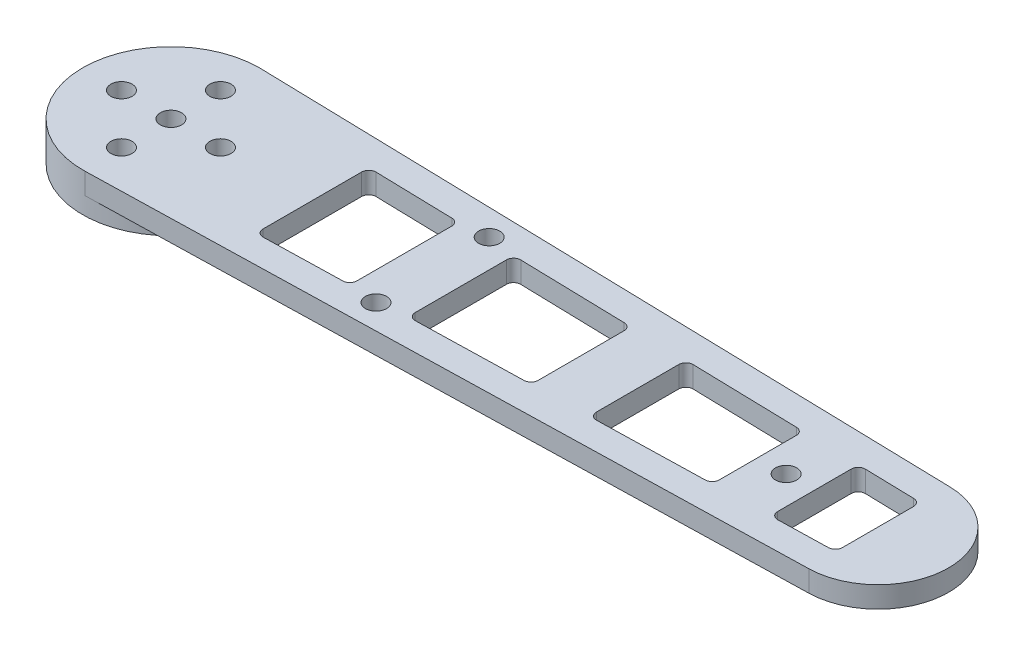
SolidWorks part; units mm, degrees
material "ABS"
ref_plane "前视基准面" through (0, 0, 0) normal (0, 0, 1) x (1, 0, 0)
ref_plane "上视基准面" through (0, 0, 0) normal (0, 1, 0) x (1, 0, 0)
ref_plane "右视基准面" through (0, 0, 0) normal (1, 0, 0) x (0, 0, -1)
sketch "草图1" plane through (0, 0, 0) normal (0, 1, 0) x (1, 0, 0)
  line L0 (-16.855, 0) -> (100, 0) construction
  line L1 (0.3125, 12.4961) -> (100.25, 9.9969)
  line L2 (0.3125, -12.4961) -> (100.25, -9.9969)
  circle A0 centre (0, 0) radius 12.5
  circle A1 centre (100, 0) radius 10
  circle A2 centre (-7, 0) radius 1.5
  circle A3 centre (0, 7) radius 1.5
  circle A4 centre (7, 0) radius 1.5
  circle A5 centre (0, -7) radius 1.5
  circle A6 centre (0, 0) radius 1.5
  dimension "D1" = 25
  dimension "D2" = 100
  dimension "D3" = 20
  dimension "D4" = 7
  dimension "D5" = 3
  dimension "D7" = 3
  dimension "D6" = 4
extrude "凸台-拉伸1" add sketch "草图1" along normal blind 3 contours A0 L0 A1 L1 | L0 A0 L2 A1 | A1 | A0 L0 A2 A4 A3 | L0 A0 A4 A2 A5 region at (0, 0, -5.4699) region at (0, 0, 5.4699) region at (49.7914, 0, -5.8152) region at (49.7914, 0, 5.8152) region at (93.2154, 0, -6.9564)
sketch "草图2" plane through (0, 0, 0) normal (0, -1, 0) x (1, 0, 0)
  circle A0 centre (0, 0) radius 12.5
  circle A1 centre (0, 0) radius 10
  dimension "D1" = 25
  dimension "D2" = 20
extrude "凸台-拉伸2" add sketch "草图2" along normal blind 2.5 contours A0 | A1
sketch "草图3" plane through (0, 3, 0) normal (0, 1, 0) x (1, 0, 0)
  line L0 (-21.5992, 0) -> (131.7448, 0) construction
  line L1 (20, 8.0025) -> (20, -8.0025)
  line L2 (20, 8.0025) -> (95.3937, 6.1171)
  line L3 (20, -8.0025) -> (100, -6.0019)
  line L4 (0.3125, 12.4961) -> (100.25, 9.9969) construction
  line L5 (0.3125, -12.4961) -> (100.25, -9.9969) construction
  line L6 (33, 7.6774) -> (33, -7.6774)
  line L7 (41, 7.4773) -> (41, -7.4773)
  line L8 (58, 7.0522) -> (58, -7.0522)
  line L9 (66, 6.8521) -> (66, -6.8521)
  line L10 (83, 6.427) -> (83, -6.427)
  line L11 (91, 6.2269) -> (91, -6.2269)
  line L12 (100, -6.0019) -> (100, 6.0019)
  line L13 (95.3937, 6.1171) -> (100, 6.0019)
  circle A1 centre (87, 0) radius 1.5
  circle A2 centre (37, 8) radius 1.5
  circle A3 centre (37, -8) radius 1.5
  point P5 (20, 0)
  dimension "D1" = 20
  dimension "D5" = 8
  dimension "D11" = 100
  dimension "D12" = 3
  dimension "D14" = 3
  dimension "D2" = 4
  dimension "D3" = 33
  dimension "D4" = 8
  dimension "D6" = 37
  dimension "D7" = 58
  dimension "D8" = 8
  dimension "83" = 83
  dimension "D10" = 8
  dimension "D13" = 4
extrude "切除-拉伸1" cut sketch "草图3" against normal blind 10 contours L1 L0 L6 L2 | L0 L1 L3 L6 | L2 A2 | L2 A2 | A3 L3 | A3 L3 | L7 L0 L8 L2 | L0 L7 L3 L8 | L9 L0 L10 L2 | L0 L9 L3 L10 | A1 L0 | L0 A1 | L11 L0 L12 L13 L2 | L0 L11 L3 L12 region at (26.4551, 3, -3.9205) region at (26.4551, 3, 3.9205) region at (49.4171, 3, -3.6334) region at (49.4171, 3, 3.6334) region at (37.0104, 3, -8.4153) region at (36.9782, 3, -7.1299) region at (36.9782, 3, 7.1299) region at (37.0104, 3, 8.4153) region at (74.4093, 3, -3.3209) region at (74.4093, 3, 3.3209) region at (87, 3, -0.6366) region at (87, 3, 0.6366) region at (95.4724, 3, -3.0576) region at (95.4724, 3, 3.0576)
fillet "圆角1" radius 1 16 edges at (100, 1.5, 6.0019) (91, 1.5, -6.2269) (100, 1.5, -6.0019) (91, 1.5, 6.2269) (66, 1.5, 6.8521) (83, 1.5, 6.427) (83, 1.5, -6.427) (66, 1.5, -6.8521) (41, 1.5, 7.4773) (41, 1.5, -7.4773) (58, 1.5, -7.0522) (58, 1.5, 7.0522) (33, 1.5, 7.6774) (33, 1.5, -7.6774) (20, 1.5, 8.0025) (20, 1.5, -8.0025)
